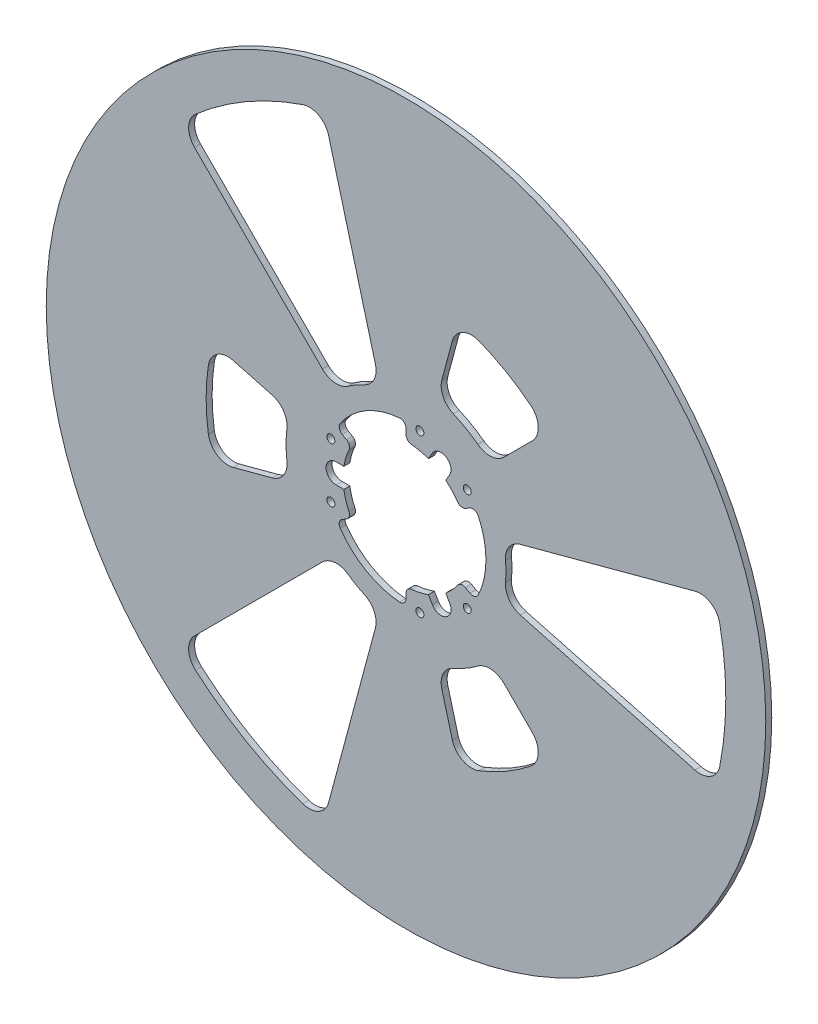
SolidWorks part; units mm, degrees
material "ABS PC"
ref_plane "Front Plane" through (0, 0, 0) normal (0, 0, 1) x (1, 0, 0)
ref_plane "Top Plane" through (0, 0, 0) normal (0, 1, 0) x (1, 0, 0)
ref_plane "Right Plane" through (0, 0, 0) normal (1, 0, 0) x (0, 0, -1)
sketch "Sketch1" plane through (0, 0, 0) normal (0, 0, 1) x (1, 0, 0)
  line L0 (-35, 5) -> (-31.1006, 5)
  line L1 (-35, -5) -> (-31.1006, -5)
  line L2 (-31.9374, 18.4391) -> (-29.7647, 17.1847)
  line L3 (-31.9374, -18.4391) -> (-29.7647, -17.1847)
  line L4 (21.8301, -27.8109) -> (19.8804, -24.4339)
  line L5 (0, -36.8782) -> (0, -34.3693)
  line L6 (13.1699, 32.8109) -> (11.2202, 29.4339)
  line L7 (31.9374, 18.4391) -> (29.7647, 17.1847)
  line L8 (13.1699, -32.8109) -> (11.2202, -29.4339)
  line L9 (31.9374, -18.4391) -> (29.7647, -17.1847)
  line L10 (21.8301, 27.8109) -> (19.8804, 24.4339)
  line L11 (0, 36.8782) -> (0, 34.3693)
  line L12 (-66.9213, -17.9315) -> (-86.395, -23.1495)
  line L13 (-66.9213, 17.9315) -> (-86.395, 23.1495)
  line L14 (17.9315, 66.9213) -> (23.1495, 86.395)
  line L15 (48.9898, -48.9898) -> (63.2456, -63.2456)
  line L16 (17.9315, -66.9213) -> (23.1495, -86.395)
  line L17 (48.9898, 48.9898) -> (63.2456, 63.2456)
  line L18 (57.1449, -15.3119) -> (144.5665, -38.7365)
  line L19 (57.1449, 15.3119) -> (144.5665, 38.7365)
  line L20 (-41.833, 41.833) -> (-105.8301, 105.8301)
  line L21 (-15.3119, -57.1449) -> (-38.7365, -144.5665)
  line L22 (-15.3119, 57.1449) -> (-38.7365, 144.5665)
  line L23 (-41.833, -41.833) -> (-105.8301, -105.8301)
  arc A0 (-35, 5) -> (-35, -5) centre (-35, 0) ccw
  circle A1 centre (-37.5877, 13.6808) radius 2
  circle A2 centre (-37.5877, -13.6808) radius 2
  arc A3 (-32.9053, 22.7429) -> (-31.9374, 18.4391) centre (-30.4374, 21.0372) ccw
  arc A4 (-28.546, 13.3182) -> (-31.1006, 5) centre (0, 0) ccw
  arc A5 (-28.546, 13.3182) -> (-29.7647, 17.1847) centre (-31.2647, 14.5866) ccw
  arc A6 (-32.9053, -22.7429) -> (-3.2432, -39.8683) centre (0, 0) ccw
  arc A7 (-29.7647, -17.1847) -> (-28.546, -13.3182) centre (-31.2647, -14.5866) ccw
  arc A8 (-31.9374, -18.4391) -> (-32.9053, -22.7429) centre (-30.4374, -21.0372) ccw
  arc A9 (-31.1006, -5) -> (-28.546, -13.3182) centre (0, 0) ccw
  arc A10 (11.2202, 29.4339) -> (2.7391, 31.3807) centre (0, 0) ccw
  arc A11 (25.8069, 18.0625) -> (29.7647, 17.1847) centre (28.2647, 19.7827) ccw
  circle A12 centre (6.9459, 39.3923) radius 2
  arc A13 (2.7391, -31.3807) -> (0, -34.3693) centre (3, -34.3693) ccw
  arc A14 (13.1699, -32.8109) -> (21.8301, -27.8109) centre (17.5, -30.3109) ccw
  arc A15 (31.9374, -18.4391) -> (36.1486, -17.1254) centre (33.4374, -15.841) ccw
  circle A16 centre (6.9459, -39.3923) radius 2
  arc A17 (29.7647, -17.1847) -> (25.8069, -18.0625) centre (28.2647, -19.7827) ccw
  arc A18 (-3.2432, -39.8683) -> (0, -36.8782) centre (-3, -36.8782) ccw
  arc A19 (25.8069, 18.0625) -> (19.8804, 24.4339) centre (0, 0) ccw
  arc A20 (19.8804, -24.4339) -> (25.8069, -18.0625) centre (0, 0) ccw
  arc A21 (2.7391, -31.3807) -> (11.2202, -29.4339) centre (0, 0) ccw
  arc A22 (0, 34.3693) -> (2.7391, 31.3807) centre (3, 34.3693) ccw
  arc A23 (36.1486, 17.1254) -> (31.9374, 18.4391) centre (33.4374, 15.841) ccw
  arc A24 (0, 36.8782) -> (-3.2432, 39.8683) centre (-3, 36.8782) ccw
  circle A25 centre (30.6418, -25.7115) radius 2
  arc A26 (21.8301, 27.8109) -> (13.1699, 32.8109) centre (17.5, 30.3109) ccw
  circle A27 centre (30.6418, 25.7115) radius 2
  arc A28 (-3.2432, 39.8683) -> (-32.9053, 22.7429) centre (0, 0) ccw
  arc A29 (36.1486, -17.1254) -> (36.1486, 17.1254) centre (0, 0) ccw
  circle A30 centre (0, 0) radius 180
  arc A31 (-59.5796, 7.0905) -> (-59.5796, -7.0905) centre (0, 0) ccw
  arc A32 (-98.8702, 14.9891) -> (-98.8702, -14.9891) centre (0, 0) ccw
  arc A33 (23.1495, -86.395) -> (36.4542, -93.1187) centre (32.8087, -83.8068) ccw
  arc A34 (17.9315, 66.9213) -> (23.6492, 55.1427) centre (27.5908, 64.3331) ccw
  arc A35 (63.2456, 63.2456) -> (62.4161, 78.1296) centre (56.1745, 70.3166) ccw
  arc A36 (23.6492, -55.1427) -> (35.9303, -48.0522) centre (0, 0) ccw
  arc A37 (23.6492, -55.1427) -> (17.9315, -66.9213) centre (27.5908, -64.3331) ccw
  arc A38 (48.9898, -48.9898) -> (35.9303, -48.0522) centre (41.9187, -56.0609) ccw
  arc A39 (35.9303, 48.0522) -> (23.6492, 55.1427) centre (0, 0) ccw
  arc A40 (62.4161, -78.1296) -> (63.2456, -63.2456) centre (56.1745, -70.3166) ccw
  arc A41 (36.4542, 93.1187) -> (23.1495, 86.395) centre (32.8087, 83.8068) ccw
  arc A42 (36.4542, -93.1187) -> (62.4161, -78.1296) centre (0, 0) ccw
  arc A43 (35.9303, 48.0522) -> (48.9898, 48.9898) centre (41.9187, 56.0609) ccw
  arc A44 (62.4161, 78.1296) -> (36.4542, 93.1187) centre (0, 0) ccw
  arc A45 (156.965, -31.0157) -> (156.965, 31.0157) centre (0, 0) ccw
  arc A46 (-86.395, 23.1495) -> (-98.8702, 14.9891) centre (-88.9832, 13.4902) ccw
  arc A47 (-98.8702, -14.9891) -> (-86.395, -23.1495) centre (-88.9832, -13.4902) ccw
  arc A48 (-66.9213, -17.9315) -> (-59.5796, -7.0905) centre (-69.5095, -8.2723) ccw
  arc A49 (-59.5796, 7.0905) -> (-66.9213, 17.9315) centre (-69.5095, 8.2723) ccw
  arc A50 (144.5665, -38.7365) -> (156.965, -31.0157) centre (147.1547, -29.0772) ccw
  arc A51 (156.965, 31.0157) -> (144.5665, 38.7365) centre (147.1547, 29.0772) ccw
  arc A52 (-105.8301, -105.8301) -> (-105.3429, -120.4279) centre (-98.759, -112.9011) ccw
  arc A53 (-105.3429, 120.4279) -> (-105.8301, 105.8301) centre (-98.759, 112.9011) ccw
  arc A54 (-51.6221, 151.4436) -> (-105.3429, 120.4279) centre (0, 0) ccw
  arc A55 (-105.3429, -120.4279) -> (-51.6221, -151.4436) centre (0, 0) ccw
  arc A56 (-51.6221, -151.4436) -> (-38.7365, -144.5665) centre (-48.3957, -141.9783) ccw
  arc A57 (-38.7365, 144.5665) -> (-51.6221, 151.4436) centre (-48.3957, 141.9783) ccw
  arc A58 (-28.9683, -40.7534) -> (-41.833, -41.833) centre (-34.7619, -48.9041) ccw
  arc A59 (-15.3119, -57.1449) -> (-20.8093, -45.464) centre (-24.9712, -54.5568) ccw
  arc A60 (57.1449, 15.3119) -> (49.7776, 4.7106) centre (59.7331, 5.6527) ccw
  arc A61 (49.7776, -4.7106) -> (49.7776, 4.7106) centre (0, 0) ccw
  arc A62 (49.7776, -4.7106) -> (57.1449, -15.3119) centre (59.7331, -5.6527) ccw
  arc A63 (-28.9683, -40.7534) -> (-20.8093, -45.464) centre (0, 0) ccw
  arc A64 (-41.833, 41.833) -> (-28.9683, 40.7534) centre (-34.7619, 48.9041) ccw
  arc A65 (-20.8093, 45.464) -> (-15.3119, 57.1449) centre (-24.9712, 54.5568) ccw
  arc A66 (-20.8093, 45.464) -> (-28.9683, 40.7534) centre (0, 0) ccw
extrude "Boss-Extrude1" add sketch "Sketch1" along normal blind 3
